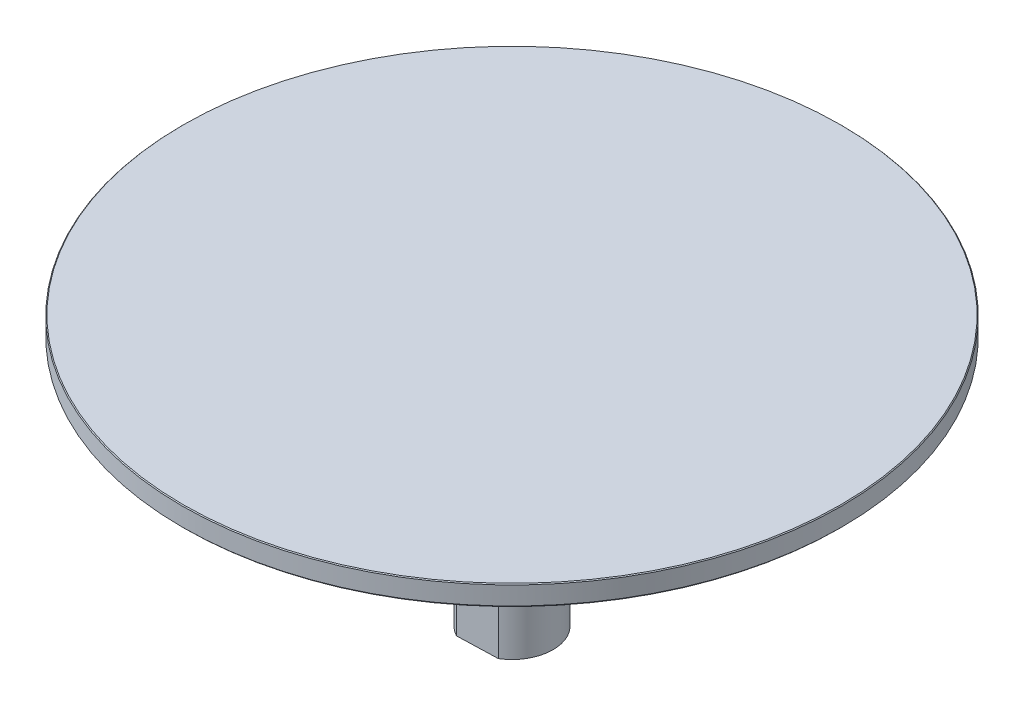
SolidWorks part; units mm, degrees
ref_plane "前视基准面" through (0, 0, 0) normal (0, 0, 1) x (1, 0, 0)
ref_plane "上视基准面" through (0, 0, 0) normal (0, 1, 0) x (1, 0, 0)
ref_plane "右视基准面" through (0, 0, 0) normal (1, 0, 0) x (0, 0, -1)
other "Configuration Table"
sketch "草图1" plane through (0, 0, 0) normal (0, 1, 0) x (1, 0, 0)
  circle A0 centre (0, 0) radius 79.5
  dimension "D1" = 159
extrude "凸台-拉伸1" add sketch "草图1" along normal blind 5
sketch "草图2" plane through (0, 0, 0) normal (0, -1, 0) x (-1, 0, 0)
  circle A0 centre (0, 0) radius 9.9
  dimension "D1" = 19.8
extrude "凸台-拉伸2" add sketch "草图2" along normal blind 60
chamfer "倒角1" distance 0.2 angle 45 1 edges at (0, 5, 79.5)
sketch "草图3" plane through (0, -60, 0) normal (0, -1, 0) x (-1, 0, 0)
  line L0 (4.8353, -8.7533) -> (-5.3657, -8.4386)
  arc A0 (-5.3657, -8.4386) -> (4.8353, -8.7533) centre (0, 0) ccw
  dimension "D1" = 20
  dimension "D2" = 8.6
extrude "切除-拉伸1" cut sketch "草图3" against normal up to surface (60 mm away) up to face at (0, 0, 9.9)
chamfer "倒角2" distance 0.4 angle 45 3 edges at (0, 0, 79.5) (0.2652, 0, 8.5959) (-0.3053, 0, -9.8953)
